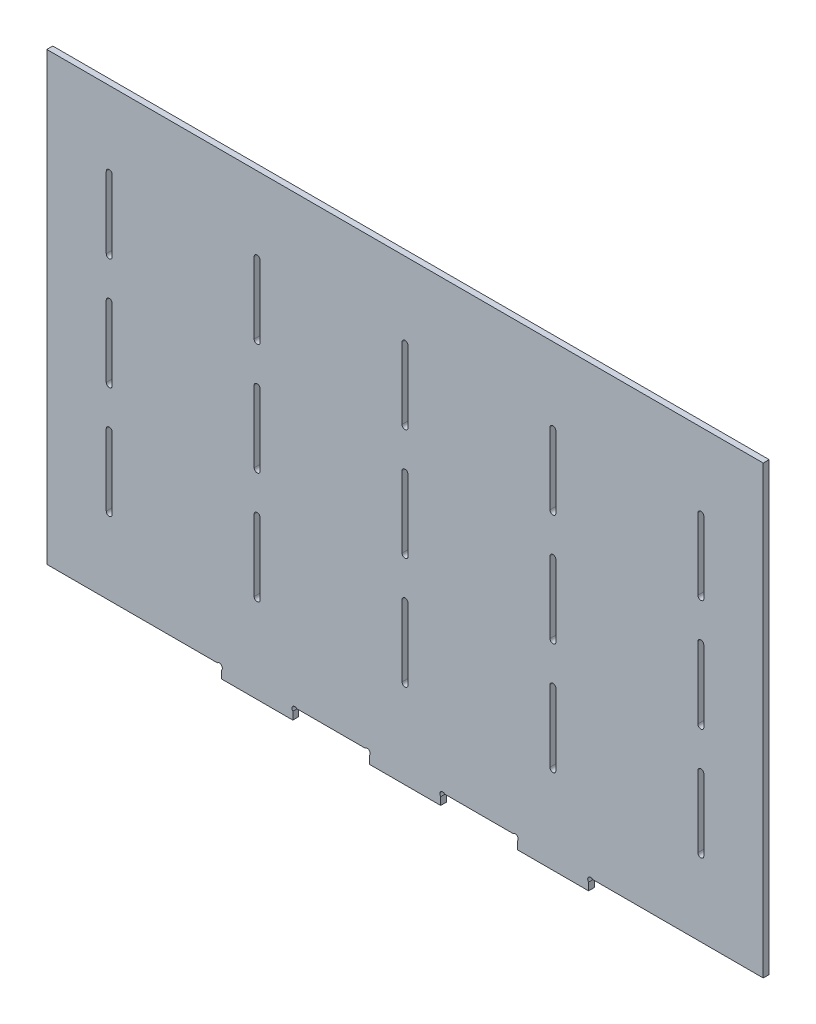
SolidWorks part; units mm, degrees
material "6061-T6 (SS)"
ref_plane "Front" through (0, 0, 0) normal (0, 0, 1) x (1, 0, 0)
ref_plane "Top" through (0, 0, 0) normal (0, 1, 0) x (1, 0, 0)
ref_plane "Right" through (0, 0, 0) normal (1, 0, 0) x (0, 0, -1)
ref_axis "Y-Axis" through (0, -50, 0) along (0, 1, 0)
sketch "Sketch1" plane through (0, 0, 0) normal (0, 0, 1) x (1, 0, 0)
  line L0 (0, 241.45) -> (0, 0) construction
  line L1 (-158.05, 0) -> (-79.025, 0) construction
  line L2 (-79.025, 0) -> (0, 0) construction
  line L3 (-79.025, 0) -> (-79.025, 241.45) construction
  line L4 (-79.025, 241.45) -> (0, 241.45) construction
  line L5 (-158.05, 241.45) -> (-79.025, 241.45) construction
  line L6 (-158.05, 241.45) -> (-237.075, 241.45) construction
  line L7 (-158.05, 0) -> (-158.05, 241.45) construction
  line L8 (-237.075, 0) -> (-158.05, 0) construction
  line L9 (-237.075, 241.45) -> (-237.075, 0) construction
  line L10 (-316.1, 0) -> (-237.075, 0) construction
  line L11 (-316.1, 0) -> (-316.1, 241.45) construction
  line L12 (-316.1, 241.45) -> (-237.075, 241.45) construction
  line L13 (0, 241.45) -> (0, 0) construction
  line L14 (-158.05, 0) -> (-79.025, 0) construction
  line L15 (-79.025, 0) -> (0, 0) construction
  line L16 (-79.025, 0) -> (-79.025, 241.45) construction
  line L17 (-79.025, 241.45) -> (0, 241.45) construction
  line L18 (-158.05, 241.45) -> (-79.025, 241.45) construction
  line L19 (-158.05, 241.45) -> (-237.075, 241.45) construction
  line L20 (-158.05, 0) -> (-158.05, 241.45) construction
  line L21 (-237.075, 0) -> (-158.05, 0) construction
  line L22 (-237.075, 241.45) -> (-237.075, 0) construction
  line L23 (-316.1, 0) -> (-237.075, 0) construction
  line L24 (-316.1, 0) -> (-316.1, 241.45) construction
  line L25 (-316.1, 241.45) -> (-237.075, 241.45) construction
  line L26 (-349.4375, 241.45) -> (33.3375, 241.45)
  line L27 (33.3375, 241.45) -> (33.3375, 3.175)
  line L28 (33.3375, 3.175) -> (-349.4375, 3.175)
  line L29 (-349.4375, 3.175) -> (-349.4375, 241.45)
  line L31 (-316.1, 0) -> (-341.5, 0) construction
  line L32 (-341.5, 0) -> (-341.5, 241.45) construction
  line L33 (-316.1, 241.45) -> (-341.5, 241.45) construction
  line L34 (-316.1, 0) -> (-341.5, 0) construction
  line L35 (-341.5, 0) -> (-341.5, 241.45) construction
  line L36 (-316.1, 241.45) -> (-341.5, 241.45) construction
  point P14 (0, 62.7437)
  point P18 (0, 122.3125)
  point P19 (0, 181.8812)
  point P22 (-316.1, 62.7437)
  point P24 (-316.1, 181.8812)
  point P32 (-316.1, 122.3125)
  dimension "D2" = 3.175
  dimension "D1" = 7.9375
extrude "Boss-Extrude1" add sketch "Sketch1" along normal mid plane 3.175 contours L26 L28 region at (-158.05, 122.3125, 0)
sketch "Sketch3" plane through (0, 0, 1.5875) normal (0, 0, 1) x (1, 0, 0)
  line L0 (33.3375, 3.175) -> (-349.4375, 3.175) construction
  line L1 (-256.125, -3.175) -> (-218.025, -3.175)
  line L2 (-256.125, -3.175) -> (-256.125, 3.175)
  line L3 (-256.125, 3.175) -> (-218.025, 3.175)
  line L4 (-218.025, -3.175) -> (-218.025, 3.175)
  line L5 (-256.125, -3.175) -> (-218.025, 3.175) construction
  line L6 (-256.125, 3.175) -> (-218.025, -3.175) construction
  line L8 (-177.1, -3.175) -> (-139, -3.175)
  line L9 (-177.1, -3.175) -> (-177.1, 3.175)
  line L10 (-177.1, 3.175) -> (-139, 3.175)
  line L11 (-139, -3.175) -> (-139, 3.175)
  line L12 (-177.1, -3.175) -> (-139, 3.175) construction
  line L13 (-177.1, 3.175) -> (-139, -3.175) construction
  line L14 (-98.075, -3.175) -> (-59.975, -3.175)
  line L15 (-98.075, -3.175) -> (-98.075, 3.175)
  line L16 (-98.075, 3.175) -> (-59.975, 3.175)
  line L17 (-59.975, -3.175) -> (-59.975, 3.175)
  line L18 (-98.075, -3.175) -> (-59.975, 3.175) construction
  line L19 (-98.075, 3.175) -> (-59.975, -3.175) construction
  point P0 (-79.025, 0)
  point P2 (-158.05, 0)
  point P4 (-237.075, 0)
  point P6 (-237.075, 0)
  point P13 (-158.05, 0)
  point P18 (-79.025, 0)
  dimension "D1" = 38.1
extrude "Weld Tabs Extrude" add sketch "Sketch3" against normal up to surface (3.175 mm away) up to face at (-158.05, 122.3125, -1.5875)
sketch "Sketch4" plane through (0, 0, 1.5875) normal (0, 0, 1) x (1, 0, 0)
  line L0 (-158.05, -3.175) -> (-158.05, 241.45) construction
  line L2 (-256.125, 3.175) -> (-257.2475, 3.175) construction
  line L3 (-256.125, 3.175) -> (-256.125, 2.0525) construction
  line L4 (-256.125, 2.0525) -> (-257.2475, 2.0525) construction
  line L5 (-257.2475, 3.175) -> (-257.2475, 2.0525) construction
  line L6 (-218.025, 3.175) -> (-216.9025, 3.175) construction
  line L7 (-218.025, 3.175) -> (-218.025, 2.0525) construction
  line L8 (-218.025, 2.0525) -> (-216.9025, 2.0525) construction
  line L9 (-216.9025, 3.175) -> (-216.9025, 2.0525) construction
  line L10 (-177.1, 3.175) -> (-178.2225, 3.175) construction
  line L11 (-177.1, 3.175) -> (-177.1, 2.0525) construction
  line L12 (-177.1, 2.0525) -> (-178.2225, 2.0525) construction
  line L13 (-178.2225, 3.175) -> (-178.2225, 2.0525) construction
  line L16 (-349.4375, 241.45) -> (-349.4375, 3.175)
  line L17 (-349.4375, 3.175) -> (-256.125, 3.175)
  line L18 (-256.125, 3.175) -> (-256.125, -3.175)
  line L19 (-256.125, -3.175) -> (-218.025, -3.175)
  line L20 (-218.025, -3.175) -> (-218.025, 3.175)
  line L21 (-218.025, 3.175) -> (-177.1, 3.175)
  line L22 (-177.1, 3.175) -> (-177.1, -3.175)
  line L23 (-177.1, -3.175) -> (-139, -3.175)
  line L24 (-139, -3.175) -> (-139, 3.175)
  line L25 (-139, 3.175) -> (-98.075, 3.175)
  line L26 (-98.075, 3.175) -> (-98.075, -3.175)
  line L27 (-98.075, -3.175) -> (-59.975, -3.175)
  line L28 (-59.975, -3.175) -> (-59.975, 3.175)
  line L29 (-59.975, 3.175) -> (33.3375, 3.175)
  line L30 (33.3375, 3.175) -> (33.3375, 241.45)
  line L31 (33.3375, 241.45) -> (-349.4375, 241.45)
  line L32 (-349.4375, 241.45) -> (-349.4375, 3.175) construction
  line L33 (-349.4375, 3.175) -> (-256.125, 3.175) construction
  line L34 (-256.125, 3.175) -> (-256.125, -3.175) construction
  line L35 (-256.125, -3.175) -> (-218.025, -3.175) construction
  line L36 (-218.025, -3.175) -> (-218.025, 3.175) construction
  line L37 (-218.025, 3.175) -> (-177.1, 3.175) construction
  line L38 (-177.1, 3.175) -> (-177.1, -3.175) construction
  line L39 (-177.1, -3.175) -> (-139, -3.175) construction
  line L40 (-139, -3.175) -> (-139, 3.175) construction
  line L41 (-139, 3.175) -> (-98.075, 3.175) construction
  line L42 (-98.075, 3.175) -> (-98.075, -3.175) construction
  line L43 (-98.075, -3.175) -> (-59.975, -3.175) construction
  line L44 (-59.975, -3.175) -> (-59.975, 3.175) construction
  line L45 (-59.975, 3.175) -> (33.3375, 3.175) construction
  line L46 (33.3375, 3.175) -> (33.3375, 241.45) construction
  line L47 (33.3375, 241.45) -> (-349.4375, 241.45) construction
  circle A0 centre (-257.2475, 2.0525) radius 1.5875
  circle A1 centre (-216.9025, 2.0525) radius 1.5875
  circle A2 centre (-178.2225, 2.0525) radius 1.5875
  circle A3 centre (-137.8775, 2.0525) radius 1.5875
  circle A4 centre (-99.1975, 2.0525) radius 1.5875
  circle A5 centre (-58.8525, 2.0525) radius 1.5875
  dimension "D2" = 3.175
extrude "Weld Tabs Tear Drop Cut" cut sketch "Sketch4" against normal up to surface (3.175 mm away) up to face at (-158.05, 30.5781, -1.5875)
sketch "Sketch6" plane through (0, 0, 1.5875) normal (0, 0, 1) x (1, 0, 0)
  line L0 (-238.6625, 200.9312) -> (-238.6625, 162.8312)
  line L1 (-317.6875, 200.9312) -> (-314.5125, 200.9312) construction
  line L2 (-317.6875, 200.9312) -> (-317.6875, 162.8312)
  line L3 (-317.6875, 162.8312) -> (-314.5125, 162.8312) construction
  line L4 (-314.5125, 200.9312) -> (-314.5125, 162.8312)
  line L5 (-317.6875, 200.9312) -> (-314.5125, 162.8312) construction
  line L6 (-317.6875, 162.8312) -> (-314.5125, 200.9312) construction
  line L7 (-235.4875, 200.9312) -> (-235.4875, 162.8312)
  line L8 (-238.6625, 200.9312) -> (-235.4875, 200.9312) construction
  line L9 (-238.6625, 162.8312) -> (-235.4875, 162.8312) construction
  line L10 (-238.6625, 200.9312) -> (-235.4875, 162.8312) construction
  line L11 (-238.6625, 162.8312) -> (-235.4875, 200.9312) construction
  line L12 (-159.6375, 200.9312) -> (-159.6375, 162.8312)
  line L13 (-156.4625, 200.9312) -> (-156.4625, 162.8312)
  line L14 (-159.6375, 200.9312) -> (-156.4625, 200.9312) construction
  line L15 (-159.6375, 162.8312) -> (-156.4625, 162.8312) construction
  line L16 (-159.6375, 200.9312) -> (-156.4625, 162.8312) construction
  line L17 (-159.6375, 162.8312) -> (-156.4625, 200.9312) construction
  line L18 (-80.6125, 200.9312) -> (-80.6125, 162.8312)
  line L19 (-77.4375, 200.9312) -> (-77.4375, 162.8312)
  line L20 (-80.6125, 200.9312) -> (-77.4375, 200.9312) construction
  line L21 (-80.6125, 162.8312) -> (-77.4375, 162.8312) construction
  line L22 (-80.6125, 200.9312) -> (-77.4375, 162.8312) construction
  line L23 (-80.6125, 162.8312) -> (-77.4375, 200.9312) construction
  line L24 (-1.5875, 200.9312) -> (-1.5875, 162.8312)
  line L25 (1.5875, 200.9312) -> (1.5875, 162.8312)
  line L26 (-1.5875, 200.9312) -> (1.5875, 200.9312) construction
  line L27 (-1.5875, 162.8312) -> (1.5875, 162.8312) construction
  line L28 (-1.5875, 200.9312) -> (1.5875, 162.8312) construction
  line L29 (-1.5875, 162.8312) -> (1.5875, 200.9312) construction
  line L30 (-238.6625, 141.3625) -> (-238.6625, 103.2625)
  line L31 (-235.4875, 141.3625) -> (-235.4875, 103.2625)
  line L32 (-238.6625, 141.3625) -> (-235.4875, 141.3625) construction
  line L33 (-238.6625, 103.2625) -> (-235.4875, 103.2625) construction
  line L34 (-238.6625, 141.3625) -> (-235.4875, 103.2625) construction
  line L35 (-238.6625, 103.2625) -> (-235.4875, 141.3625) construction
  line L36 (-159.6375, 141.3625) -> (-159.6375, 103.2625)
  line L37 (-156.4625, 141.3625) -> (-156.4625, 103.2625)
  line L38 (-159.6375, 141.3625) -> (-156.4625, 141.3625) construction
  line L39 (-159.6375, 103.2625) -> (-156.4625, 103.2625) construction
  line L40 (-159.6375, 141.3625) -> (-156.4625, 103.2625) construction
  line L41 (-159.6375, 103.2625) -> (-156.4625, 141.3625) construction
  line L42 (-80.6125, 141.3625) -> (-80.6125, 103.2625)
  line L43 (-77.4375, 141.3625) -> (-77.4375, 103.2625)
  line L44 (-80.6125, 141.3625) -> (-77.4375, 141.3625) construction
  line L45 (-80.6125, 103.2625) -> (-77.4375, 103.2625) construction
  line L46 (-80.6125, 141.3625) -> (-77.4375, 103.2625) construction
  line L47 (-80.6125, 103.2625) -> (-77.4375, 141.3625) construction
  line L48 (-1.5875, 141.3625) -> (-1.5875, 103.2625)
  line L49 (1.5875, 141.3625) -> (1.5875, 103.2625)
  line L50 (-1.5875, 141.3625) -> (1.5875, 141.3625) construction
  line L51 (-1.5875, 103.2625) -> (1.5875, 103.2625) construction
  line L52 (-1.5875, 141.3625) -> (1.5875, 103.2625) construction
  line L53 (-1.5875, 103.2625) -> (1.5875, 141.3625) construction
  line L54 (-238.6625, 81.7937) -> (-238.6625, 43.6937)
  line L55 (-235.4875, 81.7937) -> (-235.4875, 43.6937)
  line L56 (-238.6625, 81.7937) -> (-235.4875, 81.7937) construction
  line L57 (-238.6625, 43.6937) -> (-235.4875, 43.6937) construction
  line L58 (-238.6625, 81.7937) -> (-235.4875, 43.6937) construction
  line L59 (-238.6625, 43.6937) -> (-235.4875, 81.7937) construction
  line L60 (-159.6375, 81.7937) -> (-159.6375, 43.6937)
  line L61 (-156.4625, 81.7937) -> (-156.4625, 43.6937)
  line L62 (-159.6375, 81.7937) -> (-156.4625, 81.7937) construction
  line L63 (-159.6375, 43.6937) -> (-156.4625, 43.6937) construction
  line L64 (-159.6375, 81.7937) -> (-156.4625, 43.6937) construction
  line L65 (-159.6375, 43.6937) -> (-156.4625, 81.7937) construction
  line L66 (-80.6125, 81.7937) -> (-80.6125, 43.6937)
  line L67 (-77.4375, 81.7937) -> (-77.4375, 43.6937)
  line L68 (-80.6125, 81.7937) -> (-77.4375, 81.7937) construction
  line L69 (-80.6125, 43.6937) -> (-77.4375, 43.6937) construction
  line L70 (-80.6125, 81.7937) -> (-77.4375, 43.6937) construction
  line L71 (-80.6125, 43.6937) -> (-77.4375, 81.7937) construction
  line L72 (-1.5875, 81.7937) -> (-1.5875, 43.6937)
  line L73 (1.5875, 81.7937) -> (1.5875, 43.6937)
  line L74 (-1.5875, 81.7937) -> (1.5875, 81.7937) construction
  line L75 (-1.5875, 43.6937) -> (1.5875, 43.6937) construction
  line L76 (-1.5875, 81.7937) -> (1.5875, 43.6937) construction
  line L77 (-1.5875, 43.6937) -> (1.5875, 81.7937) construction
  line L78 (-317.6875, 141.3625) -> (-317.6875, 103.2625)
  line L79 (-314.5125, 141.3625) -> (-314.5125, 103.2625)
  line L80 (-317.6875, 141.3625) -> (-314.5125, 141.3625) construction
  line L81 (-317.6875, 103.2625) -> (-314.5125, 103.2625) construction
  line L82 (-317.6875, 141.3625) -> (-314.5125, 103.2625) construction
  line L83 (-317.6875, 103.2625) -> (-314.5125, 141.3625) construction
  line L84 (-317.6875, 81.7937) -> (-317.6875, 43.6937)
  line L85 (-314.5125, 81.7937) -> (-314.5125, 43.6937)
  line L86 (-317.6875, 81.7937) -> (-314.5125, 81.7937) construction
  line L87 (-317.6875, 43.6937) -> (-314.5125, 43.6937) construction
  line L88 (-317.6875, 81.7937) -> (-314.5125, 43.6937) construction
  line L89 (-317.6875, 43.6937) -> (-314.5125, 81.7937) construction
  arc A0 (-317.6875, 200.9312) -> (-314.5125, 200.9312) centre (-316.1, 200.9313) cw
  arc A1 (-317.6875, 162.8312) -> (-314.5125, 162.8312) centre (-316.1, 162.8312) ccw
  arc A2 (-238.6625, 200.9312) -> (-235.4875, 200.9312) centre (-237.075, 200.9312) cw
  arc A3 (-238.6625, 162.8312) -> (-235.4875, 162.8312) centre (-237.075, 162.8312) ccw
  arc A4 (-159.6375, 200.9312) -> (-156.4625, 200.9312) centre (-158.05, 200.9312) cw
  arc A5 (-159.6375, 162.8312) -> (-156.4625, 162.8312) centre (-158.05, 162.8312) ccw
  arc A6 (-80.6125, 200.9312) -> (-77.4375, 200.9312) centre (-79.025, 200.9312) cw
  arc A7 (-80.6125, 162.8312) -> (-77.4375, 162.8312) centre (-79.025, 162.8312) ccw
  arc A8 (-1.5875, 200.9312) -> (1.5875, 200.9312) centre (0, 200.9312) cw
  arc A9 (-1.5875, 162.8312) -> (1.5875, 162.8312) centre (0, 162.8312) ccw
  arc A10 (-238.6625, 141.3625) -> (-235.4875, 141.3625) centre (-237.075, 141.3625) cw
  arc A11 (-238.6625, 103.2625) -> (-235.4875, 103.2625) centre (-237.075, 103.2625) ccw
  arc A12 (-159.6375, 141.3625) -> (-156.4625, 141.3625) centre (-158.05, 141.3625) cw
  arc A13 (-159.6375, 103.2625) -> (-156.4625, 103.2625) centre (-158.05, 103.2625) ccw
  arc A14 (-80.6125, 141.3625) -> (-77.4375, 141.3625) centre (-79.025, 141.3625) cw
  arc A15 (-80.6125, 103.2625) -> (-77.4375, 103.2625) centre (-79.025, 103.2625) ccw
  arc A16 (-1.5875, 141.3625) -> (1.5875, 141.3625) centre (0, 141.3625) cw
  arc A17 (-1.5875, 103.2625) -> (1.5875, 103.2625) centre (0, 103.2625) ccw
  arc A18 (-238.6625, 81.7937) -> (-235.4875, 81.7937) centre (-237.075, 81.7937) cw
  arc A19 (-238.6625, 43.6937) -> (-235.4875, 43.6937) centre (-237.075, 43.6937) ccw
  arc A20 (-159.6375, 81.7937) -> (-156.4625, 81.7937) centre (-158.05, 81.7937) cw
  arc A21 (-159.6375, 43.6937) -> (-156.4625, 43.6937) centre (-158.05, 43.6937) ccw
  arc A22 (-80.6125, 81.7937) -> (-77.4375, 81.7937) centre (-79.025, 81.7937) cw
  arc A23 (-80.6125, 43.6937) -> (-77.4375, 43.6937) centre (-79.025, 43.6937) ccw
  arc A24 (-1.5875, 81.7937) -> (1.5875, 81.7937) centre (0, 81.7937) cw
  arc A25 (-1.5875, 43.6937) -> (1.5875, 43.6937) centre (0, 43.6937) ccw
  arc A26 (-317.6875, 141.3625) -> (-314.5125, 141.3625) centre (-316.1, 141.3625) cw
  arc A27 (-317.6875, 103.2625) -> (-314.5125, 103.2625) centre (-316.1, 103.2625) ccw
  arc A28 (-317.6875, 81.7937) -> (-314.5125, 81.7937) centre (-316.1, 81.7937) cw
  arc A29 (-317.6875, 43.6937) -> (-314.5125, 43.6937) centre (-316.1, 43.6937) ccw
  point P0 (-316.1, 181.8812)
  point P2 (-316.1, 181.8812)
  point P8 (0, 62.7437)
  point P12 (-237.075, 181.8812)
  point P14 (-237.075, 181.8812)
  point P21 (-158.05, 181.8812)
  point P22 (-158.05, 181.8812)
  point P29 (-79.025, 181.8812)
  point P30 (-79.025, 181.8812)
  point P37 (0, 181.8812)
  point P38 (0, 181.8812)
  point P45 (-237.075, 122.3125)
  point P46 (-237.075, 122.3125)
  point P53 (-158.05, 122.3125)
  point P54 (-158.05, 122.3125)
  point P61 (-79.025, 122.3125)
  point P62 (-79.025, 122.3125)
  point P69 (0, 122.3125)
  point P70 (0, 122.3125)
  point P77 (-237.075, 62.7437)
  point P78 (-237.075, 62.7437)
  point P85 (-158.05, 62.7437)
  point P86 (-158.05, 62.7437)
  point P93 (-79.025, 62.7437)
  point P94 (-79.025, 62.7437)
  point P101 (0, 62.7437)
  point P102 (0, 62.7437)
  point P109 (-316.1, 122.3125)
  point P110 (-316.1, 122.3125)
  point P117 (-316.1, 62.7437)
  point P118 (-316.1, 62.7437)
  dimension "D1" = 3.175
  dimension "D2" = 38.1
  dimension "D4" = 5
  dimension "D3" = 3
extrude "Weld Tabs Cutout" cut sketch "Sketch6" against normal up to surface (3.175 mm away) up to face at (-158.05, 22.7984, -1.5875)
equation "\"D2@Sketch1\"=\"acc bottom wall thickness@FS2-EN-ACC-A-0003-V1, ACCUMULATOR CONTAINER.Assembly\"/2"
equation "\"D1@Sketch3\"=\"weld slot length@FS2-EN-ACC-A-0003-V1, ACCUMULATOR CONTAINER.Assembly\""
equation "\"D2@Sketch4\"=\"weld teardrop radius@FS2-EN-ACC-A-0003-V1, ACCUMULATOR CONTAINER.Assembly\"*2"
equation "\"D1@Sketch6\"=\"acc side wall thickness@FS2-EN-ACC-A-0003-V1, ACCUMULATOR CONTAINER.Assembly\""
equation "\"D2@Sketch6\"=\"weld slot length@FS2-EN-ACC-A-0003-V1, ACCUMULATOR CONTAINER.Assembly\""
equation "\"D1@Sketch1\"=\"acc side wall thickness@FS2-EN-ACC-A-0003-V1, ACCUMULATOR CONTAINER.Assembly\"/2 + \"weld beam width@FS2-EN-ACC-A-0003-V1, ACCUMULATOR CONTAINER.Assembly\""
